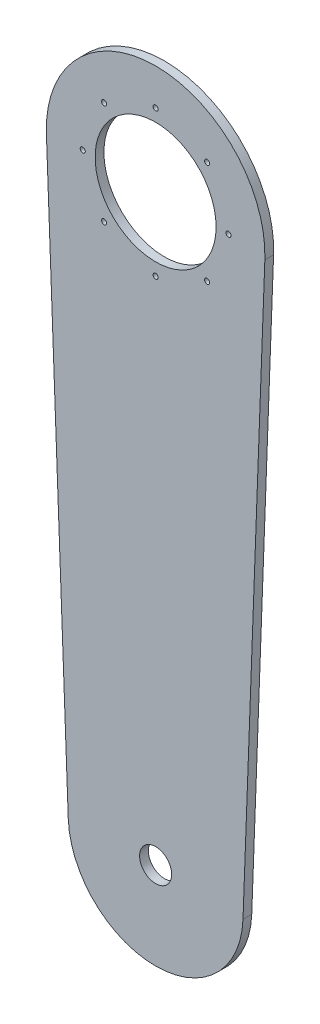
SolidWorks part; units mm, degrees
ref_plane "前视基准面" through (0, 0, 0) normal (0, 0, 1) x (1, 0, 0)
ref_plane "上视基准面" through (0, 0, 0) normal (0, 1, 0) x (1, 0, 0)
ref_plane "右视基准面" through (0, 0, 0) normal (1, 0, 0) x (0, 0, -1)
other "Configuration Table"
sketch "草图1" plane through (0, 0, 0) normal (0, 0, 1) x (1, 0, 0)
  line L0 (0, 435.7923) -> (0, -629.8791) construction
  line L1 (-74.9472, -2.8125) -> (-59.9578, -402.25)
  line L2 (74.9472, -2.8125) -> (59.9578, -402.25)
  arc A0 (74.9472, -2.8125) -> (-74.9472, -2.8125) centre (0, 0) ccw
  arc A1 (-59.9578, -402.25) -> (59.9578, -402.25) centre (0, -400) ccw
  circle A2 centre (0, 0) radius 41.5
  circle A3 centre (0, -400) radius 11
  dimension "D1" = 120
  dimension "D2" = 150
  dimension "D4" = 83
  dimension "D5" = 22
  dimension "D3" = 400
extrude "凸台-拉伸1" add sketch "草图1" along normal blind 6 contours L0 A3 | A3 L0 | A2 L0 | L0 A2 | L2 A1 L1 A0 region at (17.6131, 0, 0) region at (-17.6131, 0, 0) region at (4.6685, -400, 0) region at (-4.6685, -400, 0)
sketch "草图2" plane through (0, 0, 6) normal (0, 0, 1) x (1, 0, 0)
  line L0 (0, 0) -> (50, 0) construction
  circle A0 centre (50, 0) radius 1.75
  circle A1 centre (35.3553, -35.3553) radius 1.75
  circle A2 centre (0, -50) radius 1.75
  circle A3 centre (-35.3553, -35.3553) radius 1.75
  circle A4 centre (-50, 0) radius 1.75
  circle A5 centre (-35.3553, 35.3553) radius 1.75
  circle A6 centre (0, 50) radius 1.75
  circle A7 centre (35.3553, 35.3553) radius 1.75
  point P20 (0, 0)
  dimension "D1" = 3.5
  dimension "D2" = 50
  dimension "D3" = 8
extrude "切除-拉伸1" cut sketch "草图2" against normal blind 10
equation "\"、\"=6"
